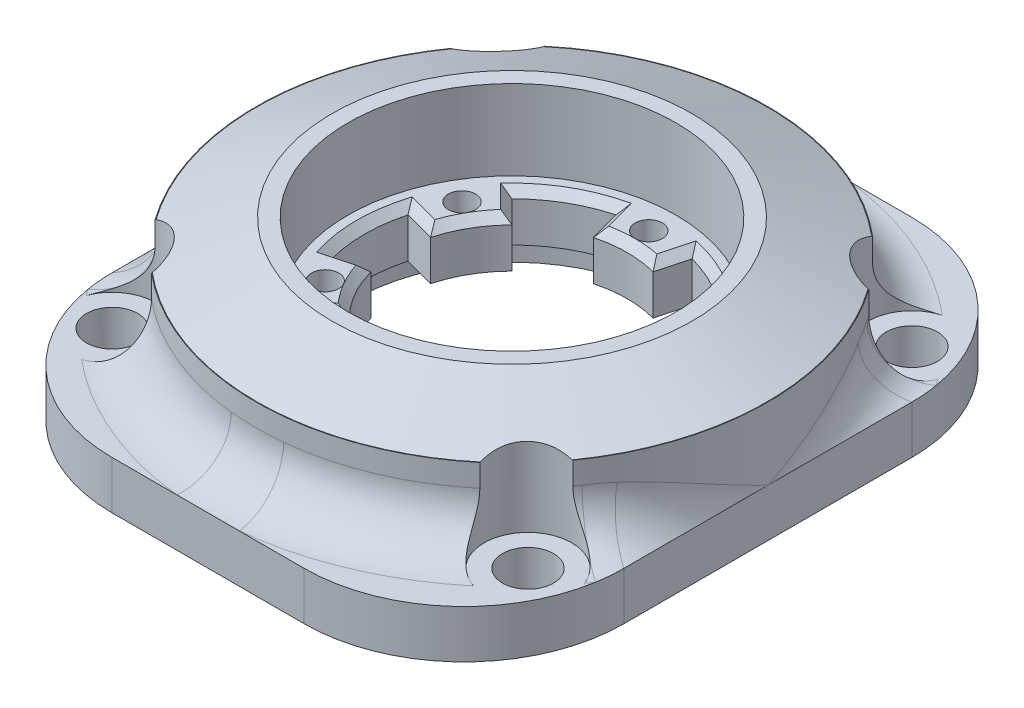
SolidWorks part; units mm, degrees
ref_plane "정면" through (0, 0, 0) normal (0, 0, 1) x (1, 0, 0)
ref_plane "윗면" through (0, 0, 0) normal (0, 1, 0) x (1, 0, 0)
ref_plane "우측면" through (0, 0, 0) normal (1, 0, 0) x (0, 0, -1)
sketch "스케치1" plane through (0, 0, 0) normal (0, 1, 0) x (1, 0, 0)
  circle A0 centre (0, 0) radius 16
  dimension "D1" = 32
extrude "보스-돌출1" add sketch "스케치1" along normal blind 6
sketch "스케치2" plane through (0, 6, 0) normal (0, 1, 0) x (1, 0, 0)
  circle A0 centre (0, 0) radius 10.25
  dimension "D1" = 20.5
extrude "컷-돌출1" cut sketch "스케치2" against normal blind 3
sketch "스케치3" plane through (0, 3, 0) normal (0, 1, 0) x (1, 0, 0)
  circle A0 centre (0, 0) radius 7.2
  dimension "D1" = 14.4
extrude "컷-돌출2" cut sketch "스케치3" against normal through all
sketch "스케치4" plane through (0, 6, 0) normal (0, 1, 0) x (1, 0, 0)
  circle A0 centre (0, 0) radius 11.25
  circle A1 centre (0, 0) radius 10.25
  dimension "D1" = 1
extrude "보스-돌출2" add sketch "스케치4" along normal blind 2
sketch "스케치5" plane through (0, 3, 0) normal (0, 1, 0) x (1, 0, 0)
  line L24 (-1.8635, 6.9547) -> (-2.3811, 8.8865)
  line L25 (5.0912, 5.0912) -> (6.5054, 6.5054)
  line L26 (6.9547, -1.8635) -> (8.8865, -2.3811)
  line L27 (1.8635, -6.9547) -> (2.3811, -8.8865)
  line L28 (-5.0912, -5.0912) -> (-6.5054, -6.5054)
  line L29 (-6.9547, 1.8635) -> (-8.8865, 2.3811)
  line L30 (-5.0912, 5.0912) -> (-6.5054, 6.5054)
  line L31 (6.9547, 1.8635) -> (8.8865, 2.3811)
  line L32 (1.8635, 6.9547) -> (2.3811, 8.8865)
  line L33 (5.0912, -5.0912) -> (6.5054, -6.5054)
  line L34 (-1.8635, -6.9547) -> (-2.3811, -8.8865)
  line L35 (-6.9547, -1.8635) -> (-8.8865, -2.3811)
  arc A7 (-2.3811, 8.8865) -> (-6.5054, 6.5054) centre (0, 0) ccw
  arc A8 (6.5054, 6.5054) -> (2.3811, 8.8865) centre (0, 0) ccw
  arc A9 (-8.8865, 2.3811) -> (-8.8865, -2.3811) centre (0, 0) ccw
  arc A10 (-6.5054, -6.5054) -> (-2.3811, -8.8865) centre (0, 0) ccw
  arc A11 (2.3811, -8.8865) -> (6.5054, -6.5054) centre (0, 0) ccw
  arc A12 (8.8865, -2.3811) -> (8.8865, 2.3811) centre (0, 0) ccw
  arc A13 (5.0912, 5.0912) -> (1.8635, 6.9547) centre (0, 0) ccw
  arc A14 (-1.8635, 6.9547) -> (-5.0912, 5.0912) centre (0, 0) ccw
  arc A15 (-6.9547, 1.8635) -> (-6.9547, -1.8635) centre (0, 0) ccw
  arc A16 (-5.0912, -5.0912) -> (-1.8635, -6.9547) centre (0, 0) ccw
  arc A17 (1.8635, -6.9547) -> (5.0912, -5.0912) centre (0, 0) ccw
  arc A18 (6.9547, -1.8635) -> (6.9547, 1.8635) centre (0, 0) ccw
  point P14 (0, 0)
  point P16 (0, 0)
  point P29 (0, 0)
  point P43 (0, 0)
  point P57 (0, 0)
extrude "컷-돌출3" cut sketch "스케치5" against normal through all
chamfer "모따기1" distance 0.5 angle 45 24 edges at (9.2, 3, 0) (4.6, 3, -7.9674) (-4.6, 3, -7.9674) (-9.2, 3, 0) (-4.6, 3, 7.9674) (4.6, 3, 7.9674) (7.9206, 3, -2.1223) (6.2354, 3, -3.6) (5.7983, 3, -5.7983) (2.1223, 3, -7.9206) (0, 3, -7.2) (-2.1223, 3, -7.9206) (-5.7983, 3, -5.7983) (-6.2354, 3, -3.6) (-7.9206, 3, -2.1223) (-7.9206, 3, 2.1223) (-6.2354, 3, 3.6) (-5.7983, 3, 5.7983) (-2.1223, 3, 7.9206) (0, 3, 7.2) (2.1223, 3, 7.9206) (5.7983, 3, 5.7983) (6.2354, 3, 3.6) (7.9206, 3, 2.1223)
draft "구배1" type of draft neutral plane draft angle 67 faces to draft 1 face at (0, 8, 11.25) neutral plane through (0, 8, 0) neutral plane normal (0, 1, 0) parameters "D1"=67
sketch "스케치6" plane through (0, 3, 0) normal (0, 1, 0) x (1, 0, 0)
  circle A0 centre (0, 0) radius 8.55 construction
  circle A1 centre (0, 8.55) radius 0.85
  circle A2 centre (7.4045, 4.275) radius 0.85
  circle A3 centre (7.4045, -4.275) radius 0.85
  circle A4 centre (0, -8.55) radius 0.85
  circle A5 centre (-7.4045, -4.275) radius 0.85
  circle A6 centre (-7.4045, 4.275) radius 0.85
  point P17 (0, 0)
  dimension "D1" = 17.1
  dimension "D2" = 1.7
  dimension "D3" = 6
extrude "컷-돌출4" cut sketch "스케치6" against normal through all
sketch "스케치7" plane through (0, 0, 0) normal (0, -1, 0) x (-1, 0, 0)
  line L1 (16, 19) -> (-16, 19)
  line L2 (16, 19) -> (16, -19)
  line L3 (16, -19) -> (-16, -19)
  line L4 (-16, 19) -> (-16, -19)
  line L5 (16, 19) -> (-16, -19) construction
  line L6 (16, -19) -> (-16, 19) construction
  circle A0 centre (0, 0) radius 10
  point P0 (0, 0)
  dimension "D3" = 20
  dimension "D1" = 32
  dimension "D2" = 38
extrude "보스-돌출3" add sketch "스케치7" along normal mid plane 3
fillet "필렛2" radius 10 4 edges at (-16, 0, 19) (16, 0, 19) (16, 0, -19) (-16, 0, -19)
fillet "필렛5" radius 3.1 2 edges at (0, 1.5, 16) (0, 1.5, -16)
sketch "스케치8" plane through (0, -1.5, 0) normal (0, -1, 0) x (1, 0, 0)
  line L0 (6, 19) -> (-6, 19) construction
  line L3 (-13, 12) -> (13, 12) construction
  line L7 (-13, 12) -> (-13, -12) construction
  line L8 (-13, -12) -> (13, -12) construction
  line L9 (13, 12) -> (13, -12) construction
  line L10 (-13, 12) -> (13, -12) construction
  line L11 (-13, -12) -> (13, 12) construction
  line L12 (-6, -19) -> (6, -19) construction
  line L13 (16, -9) -> (16, 9) construction
  line L15 (-16, 9) -> (-16, -9) construction
  circle A4 centre (-13, 12) radius 1.6
  circle A5 centre (13, 12) radius 1.6
  circle A6 centre (-13, -12) radius 1.6
  circle A7 centre (13, -12) radius 1.6
  point P4 (0, 0)
  dimension "D1" = 7
  dimension "D2" = 7
  dimension "D3" = 3
  dimension "D4" = 3
  dimension "D5" = 3.2
extrude "컷-돌출5" cut sketch "스케치8" against normal through all
sketch "스케치9" plane through (0, 8, 0) normal (0, 1, 0) x (1, 0, 0)
  circle A0 centre (-13, 12) radius 2.75
  circle A1 centre (13, 12) radius 2.75
  circle A2 centre (-13, -12) radius 2.75
  circle A3 centre (13, -12) radius 2.75
  dimension "D1" = 5.5
extrude "컷-돌출6" cut sketch "스케치9" along normal blind 5.5 from surface starting at face at (-10.8092, 1.5, 15.497)
